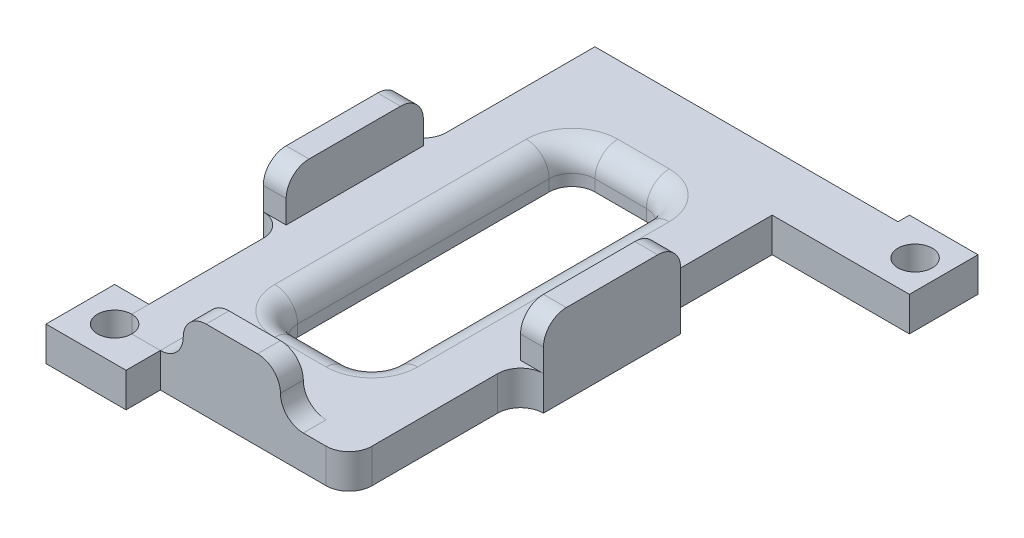
SolidWorks part; units mm, degrees
ref_plane "前视基准面" through (0, 0, 0) normal (0, 0, 1) x (1, 0, 0)
ref_plane "上视基准面" through (0, 0, 0) normal (0, 1, 0) x (1, 0, 0)
ref_plane "右视基准面" through (0, 0, 0) normal (1, 0, 0) x (0, 0, -1)
other "Configuration Table"
sketch "草图1" plane through (0, 0, 0) normal (0, 1, 0) x (1, 0, 0)
  line L1 (0, 0) -> (-20.5, 0)
  line L2 (0, 0) -> (0, 15)
  line L3 (0, 42) -> (-20.5, 42)
  line L4 (-20.5, 0) -> (-20.5, 15)
  line L5 (-20.5, 21) -> (-22.5, 21) construction
  line L7 (-20.5, 27) -> (-22.5, 27)
  line L8 (-22.5, 15) -> (-22.5, 27)
  line L9 (-20.5, 15) -> (-22.5, 15)
  line L10 (0, 15) -> (2, 15)
  line L11 (2, 15) -> (2, 27)
  line L12 (0, 27) -> (2, 27)
  line L13 (-20.5, 27) -> (-20.5, 42)
  line L14 (0, 27) -> (0, 42)
  point P9 (0, 0)
  point P10 (2, 16)
  point P17 (0, 16)
  point P18 (0, 0)
  dimension "D1" = 20.5
  dimension "D2" = 42
  dimension "D3" = 12
  dimension "D4" = 12
  dimension "D5" = 21
  dimension "D6" = 15
  dimension "D7" = 2
  dimension "D8" = 2
  dimension "D9" = 90
  dimension "D10" = 90
extrude "凸台-拉伸1" add sketch "草图1" along normal blind 3
sketch "草图3" plane through (0, 3, 0) normal (0, 1, 0) x (1, 0, 0)
  line L0 (-20.5, 0) -> (0, 0) construction
  line L1 (-14.5, 0) -> (-6, 0)
  line L2 (-14.5, 0) -> (-14.5, 2)
  line L3 (-14.5, 2) -> (-6, 2)
  line L4 (-6, 0) -> (-6, 2)
  line L5 (-20.5, 15) -> (-20.5, 0) construction
  line L6 (0, 0) -> (0, 15) construction
  line L7 (-22.5, 21) -> (-16.3156, 21) construction
  line L8 (-22.5, 27) -> (-22.5, 15) construction
  dimension "D1" = 2
  dimension "D2" = 6
  dimension "D3" = 6
extrude "凸台-拉伸2" add sketch "草图3" along normal blind 4
sketch "草图4" plane through (0, 3, 0) normal (0, 1, 0) x (1, 0, 0)
  line L1 (-22.5, 27) -> (-20.5, 27)
  line L2 (-22.5, 27) -> (-22.5, 15)
  line L3 (-22.5, 15) -> (-20.5, 15)
  line L4 (-20.5, 27) -> (-20.5, 15)
  line L5 (0, 15) -> (2, 15)
  line L6 (0, 15) -> (0, 27)
  line L7 (0, 27) -> (2, 27)
  line L8 (2, 15) -> (2, 27)
extrude "凸台-拉伸3" add sketch "草图4" along normal blind 4
fillet "圆角1" radius 2 6 edges at (-14.5, 7, -1) (-6, 7, -1) (1, 7, -27) (1, 7, -15) (-21.5, 7, -27) (-21.5, 7, -15)
fillet "圆角2" radius 2 1 edges at (0, 1.5, 0)
fillet "圆角3" radius 2 6 edges at (-6, 3, -1) (-14.5, 3, -1) (-20.5, 1.5, -15) (-20.5, 1.5, -27) (0, 1.5, -27) (0, 1.5, -15)
sketch "草图5" plane through (0, 3, 0) normal (0, 1, 0) x (1, 0, 0)
  line L0 (0, 29) -> (0, 42) construction
  line L1 (-14.5, 34) -> (-6, 34)
  line L2 (-14.5, 34) -> (-14.5, 8)
  line L3 (-14.5, 8) -> (-6, 8)
  line L4 (-6, 34) -> (-6, 8)
  line L5 (-20.5, 42) -> (-20.5, 29) construction
  line L6 (0, 42) -> (-20.5, 42) construction
  line L7 (-4, 2) -> (-16.5, 2) construction
  dimension "D1" = 6
  dimension "D2" = 6
  dimension "D3" = 8
  dimension "D4" = 6
extrude "切除-拉伸1" cut sketch "草图5" against normal blind 4
fillet "圆角4" radius 2 8 edges at (-14.5, 3, -21) (-10.25, 3, -8) (-10.25, 3, -34) (-6, 3, -21) (-6, 1.5, -8) (-14.5, 1.5, -8) (-6, 1.5, -34) (-14.5, 1.5, -34)
sketch "草图7" plane through (0, 3, 0) normal (0, 1, 0) x (1, 0, 0)
  line L0 (-16.5, 0) -> (-16.5, -3)
  line L1 (-16.5, -3) -> (-23.5, -3)
  line L2 (-23.5, -3) -> (-23.5, 3)
  line L3 (-23.5, 3) -> (-20.5, 3)
  line L4 (-20.5, 13) -> (-20.5, 0) construction
  line L5 (-20.5, 3) -> (-20.5, 0)
  line L6 (-20.5, 0) -> (-16.5, 0)
  dimension "D1" = 3
  dimension "D2" = 7
  dimension "D3" = 3
extrude "凸台-拉伸4" add sketch "草图7" against normal blind 3 separate body
sketch "草图9" plane through (0, 0, 0) normal (1, 0, 0) x (0, 0, -1)
  line L0 (29, 3) -> (42, 3) construction
  line L1 (42, 0) -> (37, 0)
  line L2 (42, 0) -> (42, 3)
  line L3 (42, 3) -> (37, 3)
  line L4 (37, 0) -> (37, 3)
  dimension "D1" = 5
extrude "凸台-拉伸5" add sketch "草图9" along normal blind 12
sketch "草图8" plane through (0, 3, 0) normal (0, 1, 0) x (1, 0, 0)
  line L0 (-20.5, 0) -> (9.5, 0) construction
  line L1 (9.5, 0) -> (9.5, 40) construction
  circle A0 centre (-20.5, 0) radius 1.5
  circle A1 centre (9.5, 40) radius 1.5
  dimension "D1" = 3
  dimension "D4" = 3
  dimension "D2" = 30
  dimension "D3" = 40
extrude "切除-拉伸2" cut sketch "草图8" against normal blind 12
sketch "草图10" plane through (0, 0, -42) normal (0, 0, -1) x (-1, 0, 0)
  line L0 (-12, 0) -> (20.5, 0) construction
  line L1 (-12, 3) -> (-6, 3)
  line L2 (-12, 3) -> (-12, 0)
  line L3 (-12, 0) -> (-6, 0)
  line L4 (-6, 3) -> (-6, 0)
  dimension "D1" = 6
extrude "凸台-拉伸6" add sketch "草图10" along normal blind 1
